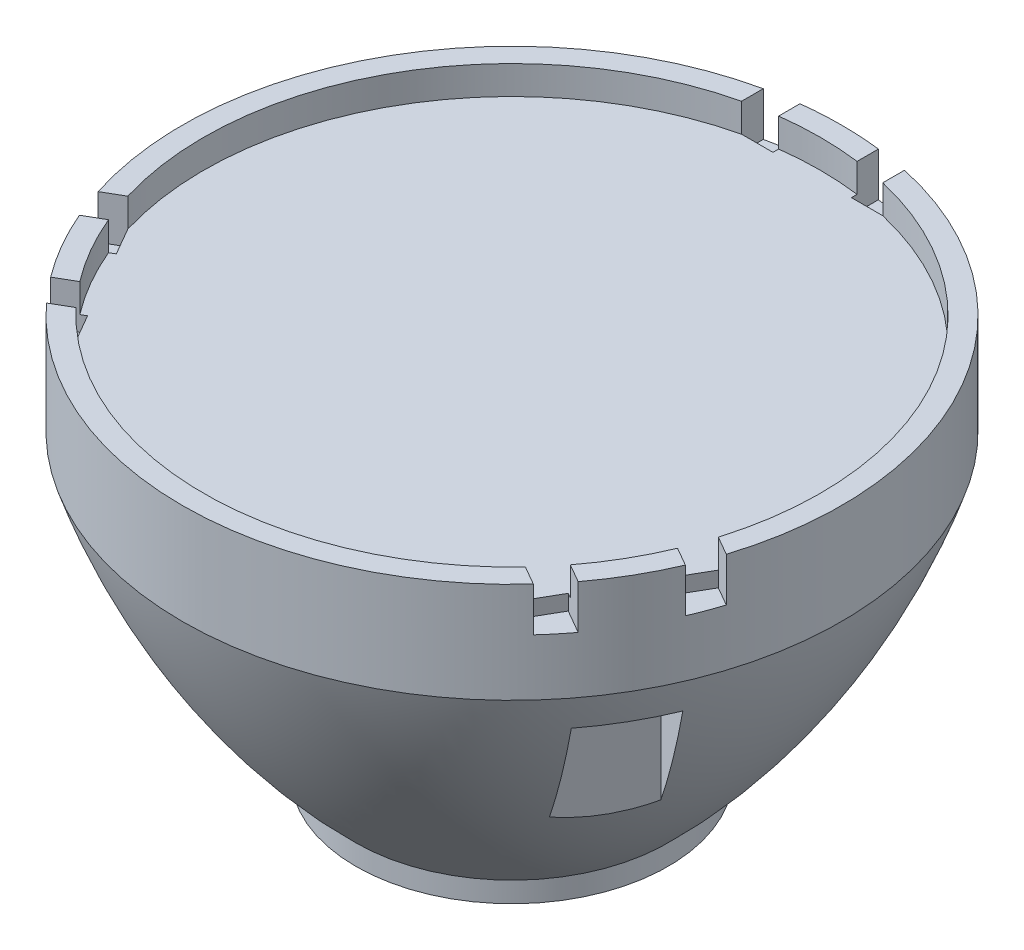
SolidWorks part; units mm, degrees
material "PMMA"
ref_plane "Front Plane" through (0, 0, 0) normal (0, 0, 1) x (1, 0, 0)
ref_plane "Top Plane" through (0, 0, 0) normal (0, 1, 0) x (1, 0, 0)
ref_plane "Right Plane" through (0, 0, 0) normal (1, 0, 0) x (0, 0, -1)
sketch "Sketch1" plane through (0, 0, 0) normal (0, 0, 1) x (1, 0, 0)
  line L0 (0, 0) -> (0, 5.7613) construction
  line L1 (0, 0) -> (4.975, 0)
  line L2 (4.975, 0) -> (4.975, 0.65)
  line L3 (10.5, 9.52) -> (10.5, 12.72)
  line L4 (10.5, 12.72) -> (0, 12.72)
  line L5 (0, 0) -> (0, 12.72)
  line L6 (5.8905, 1.6) -> (0, 1.6) construction
  arc A0 (4.975, 0.65) -> (10.5, 9.52) centre (-10.4019, 16.3838) ccw
  dimension "D6" = 22
  dimension "D1" = 12.72
  dimension "D2" = 0.65
  dimension "D3" = 3.2
  dimension "D4" = 4.975
  dimension "D5" = 10.5
  dimension "D7" = 1.6
  dimension "D8" = 5.8905
revolve "Lens Holder" add sketch "Sketch1" angle 360 about L0
sketch "Sketch3" plane through (0, 12.72, 0) normal (0, 1, 0) x (1, 0, 0)
  circle A0 centre (0, 0) radius 9.825
  dimension "D1" = 19.65
extrude "Lens Top Cut-Extrude2" cut sketch "Sketch3" against normal blind 0.91
sketch "Sketch2" plane through (0, 12.72, 0) normal (0, 1, 0) x (1, 0, 0)
  line L0 (0, 0) -> (0, 10.5) construction
  line L1 (8.4036, -6.2952) -> (7.9036, -7.1612)
  line L2 (1.25, 10.4253) -> (2.25, 10.4253)
  line L3 (1.25, 10.4253) -> (1.25, 9.5639)
  line L4 (1.25, 9.5639) -> (2.25, 9.5639)
  line L5 (2.25, 10.4253) -> (2.25, 9.5639)
  line L6 (-2.25, 10.4253) -> (-1.25, 10.4253)
  line L7 (-2.25, 10.4253) -> (-2.25, 9.5639)
  line L8 (-2.25, 9.5639) -> (-1.25, 9.5639)
  line L9 (-1.25, 10.4253) -> (-1.25, 9.5639)
  line L10 (7.9036, -7.1612) -> (7.1576, -6.7305)
  line L11 (7.6576, -5.8645) -> (7.1576, -6.7305)
  line L12 (8.4036, -6.2952) -> (7.6576, -5.8645)
  line L13 (10.1536, -3.2641) -> (9.6536, -4.1301)
  line L14 (9.4076, -2.8334) -> (8.9076, -3.6994)
  line L15 (9.6536, -4.1301) -> (8.9076, -3.6994)
  line L16 (10.1536, -3.2641) -> (9.4076, -2.8334)
  line L17 (-9.6536, -4.1301) -> (-10.1536, -3.2641)
  line L18 (-10.1536, -3.2641) -> (-9.4076, -2.8334)
  line L19 (-8.9076, -3.6994) -> (-9.4076, -2.8334)
  line L20 (-9.6536, -4.1301) -> (-8.9076, -3.6994)
  line L21 (-7.9036, -7.1612) -> (-8.4036, -6.2952)
  line L22 (-7.1576, -6.7305) -> (-7.6576, -5.8645)
  line L23 (-8.4036, -6.2952) -> (-7.6576, -5.8645)
  line L24 (-7.9036, -7.1612) -> (-7.1576, -6.7305)
  circle A0 centre (0, 0) radius 10.5 construction
  circle A1 centre (0, 0) radius 9.825 construction
  point P33 (0, 0)
  dimension "D1" = 1
  dimension "D2" = 4.5
  dimension "D3" = 3
extrude "Top Cut-Extrude3" cut sketch "Sketch2" against normal blind 1.4
sketch "Sketch4" plane through (0, 0, 0) normal (0, -1, 0) x (1, 0, 0)
  line L0 (2.49, 1.8) -> (1.99, 1.3)
  line L1 (-2.49, 2.49) -> (-1.8, 2.49)
  line L2 (-2.49, 2.49) -> (-2.49, 1.8)
  line L3 (-2.49, -2.49) -> (-1.8, -2.49)
  line L4 (2.49, 2.49) -> (2.49, 1.8)
  line L5 (1.99, 1.3) -> (2.49, 0.8)
  line L6 (0, 0) -> (2.49, 0) construction
  line L7 (1.99, -1.3) -> (2.49, -0.8)
  line L8 (2.49, -1.8) -> (1.99, -1.3)
  line L9 (2.49, 0.8) -> (2.49, -0.8)
  line L10 (2.49, -1.8) -> (2.49, -2.49)
  line L11 (-1.8, -2.49) -> (-1.3, -1.99)
  line L12 (-1.3, -1.99) -> (-0.8, -2.49)
  line L13 (1.3, -1.99) -> (0.8, -2.49)
  line L14 (1.8, -2.49) -> (1.3, -1.99)
  line L15 (-2.49, 1.8) -> (-1.99, 1.3)
  line L16 (-1.99, 1.3) -> (-2.49, 0.8)
  line L17 (-1.99, -1.3) -> (-2.49, -0.8)
  line L18 (-2.49, -1.8) -> (-1.99, -1.3)
  line L19 (1.8, 2.49) -> (1.3, 1.99)
  line L20 (1.3, 1.99) -> (0.8, 2.49)
  line L21 (-1.3, 1.99) -> (-0.8, 2.49)
  line L22 (-1.8, 2.49) -> (-1.3, 1.99)
  line L23 (1.8, -2.49) -> (2.49, -2.49)
  line L24 (-0.8, -2.49) -> (0.8, -2.49)
  line L25 (-2.49, -1.8) -> (-2.49, -2.49)
  line L26 (-2.49, 0.8) -> (-2.49, -0.8)
  line L27 (-0.8, 2.49) -> (0.8, 2.49)
  line L28 (1.8, 2.49) -> (2.49, 2.49)
  circle A0 centre (0, 0) radius 2.49 construction
  point P35 (0, 0)
  dimension "D1" = 4.98
  dimension "D2" = 1
  dimension "D3" = 0.5
  dimension "D4" = 2.6
  dimension "D5" = 4
extrude "Bottom Cut-Extrude4" cut sketch "Sketch4" against normal blind 0.8
ref_plane "Plane1" through (0, 9.52, 0) normal (0, 1, 0) x (1, 0, 0)
sketch "Sketch5" plane through (0, 9.52, 0) normal (0, 1, 0) x (1, 0, 0)
  line L0 (0, 0) -> (0, 10.5) construction
  line L1 (-1.3, 10.4192) -> (1.3, 10.4192) construction
  line L2 (-1.3, 10.016) -> (-1.3, 8.1)
  line L3 (-1.3, 8.1) -> (1.3, 8.1)
  line L4 (1.3, 10.016) -> (1.3, 8.1)
  line L5 (1.3, 10.016) -> (1.3, 10.4192) construction
  line L6 (-1.3, 10.016) -> (-1.3, 10.4192) construction
  line L7 (8.0241, -6.1338) -> (6.3648, -5.1758)
  line L8 (7.6648, -2.9242) -> (6.3648, -5.1758)
  line L9 (9.3241, -3.8822) -> (7.6648, -2.9242)
  line L10 (-9.3241, -3.8822) -> (-7.6648, -2.9242)
  line L11 (-6.3648, -5.1758) -> (-7.6648, -2.9242)
  line L12 (-8.0241, -6.1338) -> (-6.3648, -5.1758)
  circle A0 centre (0, 0) radius 10.5 construction
  arc A1 (-1.3, 10.016) -> (1.3, 10.016) centre (0, 0) cw
  arc A2 (9.3241, -3.8822) -> (8.0241, -6.1338) centre (0, 0) cw
  arc A3 (-8.0241, -6.1338) -> (-9.3241, -3.8822) centre (0, 0) cw
  point P22 (0, 0)
  dimension "D2" = 0.4
  dimension "D1" = 2.6
  dimension "D4" = 2.4
  dimension "D3" = 3
extrude "Side Cut-Extrude5" cut sketch "Sketch5" against normal blind 8
sketch "Sketch6" plane through (0, 0.8, 0) normal (0, -1, 0) x (1, 0, 0)
  circle A0 centre (0, 0) radius 2.6
  dimension "D1" = 5.2
extrude "Lens Hole Cut-Extrude7" cut sketch "Sketch6" against normal blind 5
equation "\"D4@Sketch1\"=9.95/2"
equation "\"D5@Sketch1\"=21/2"
